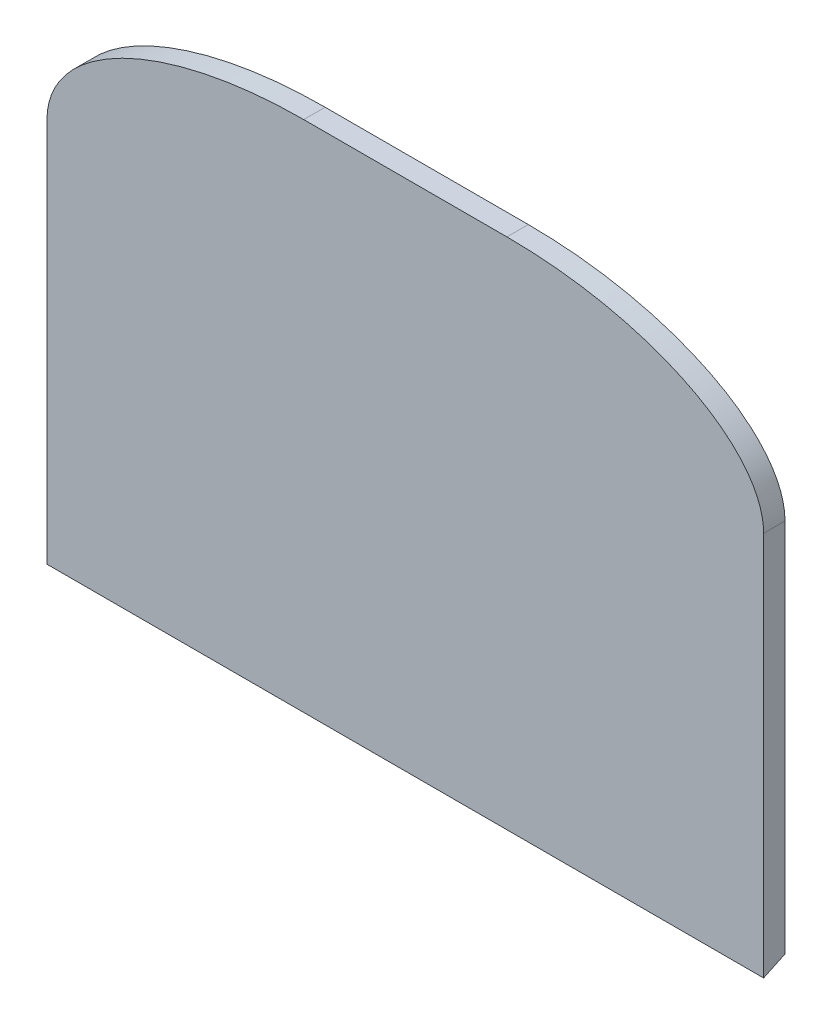
SolidWorks part; units mm, degrees
ref_plane "Front Plane" through (0, 0, 0) normal (0, 0, 1) x (1, 0, 0)
ref_plane "Top Plane" through (0, 0, 0) normal (0, 1, 0) x (1, 0, 0)
ref_plane "Right Plane" through (0, 0, 0) normal (1, 0, 0) x (0, 0, -1)
sketch "Sketch2" plane through (0, 0, 0) normal (1, 0, 0) x (0, 0, -1)
  line L0 (0, 429.1364) -> (0, 439.1364) construction
  line L1 (0, 222.0243) -> (0, 520.8304)
  line L2 (-121.6261, 164.6222) -> (-144.5964, 153.7812) construction
  line L3 (0, 222.0243) -> (-12.7, 216.0304)
  line L4 (2.54, 223.223) -> (-121.6261, 164.6222) construction
  line L5 (-12.7, 216.0304) -> (-12.7, 520.8304)
  line L6 (-12.7, 520.8304) -> (0, 520.8304)
  dimension "D1" = 12.7
  dimension "D2" = 304.8
extrude "Boss-Extrude1" add sketch "Sketch2" along normal up to surface (212.7 mm away) and the other way up to surface (212.7 mm away)
fillet "Fillet1" radius 152.4 2 edges at (-212.7, 520.8304, 6.35) (212.7, 520.8304, 6.35)
